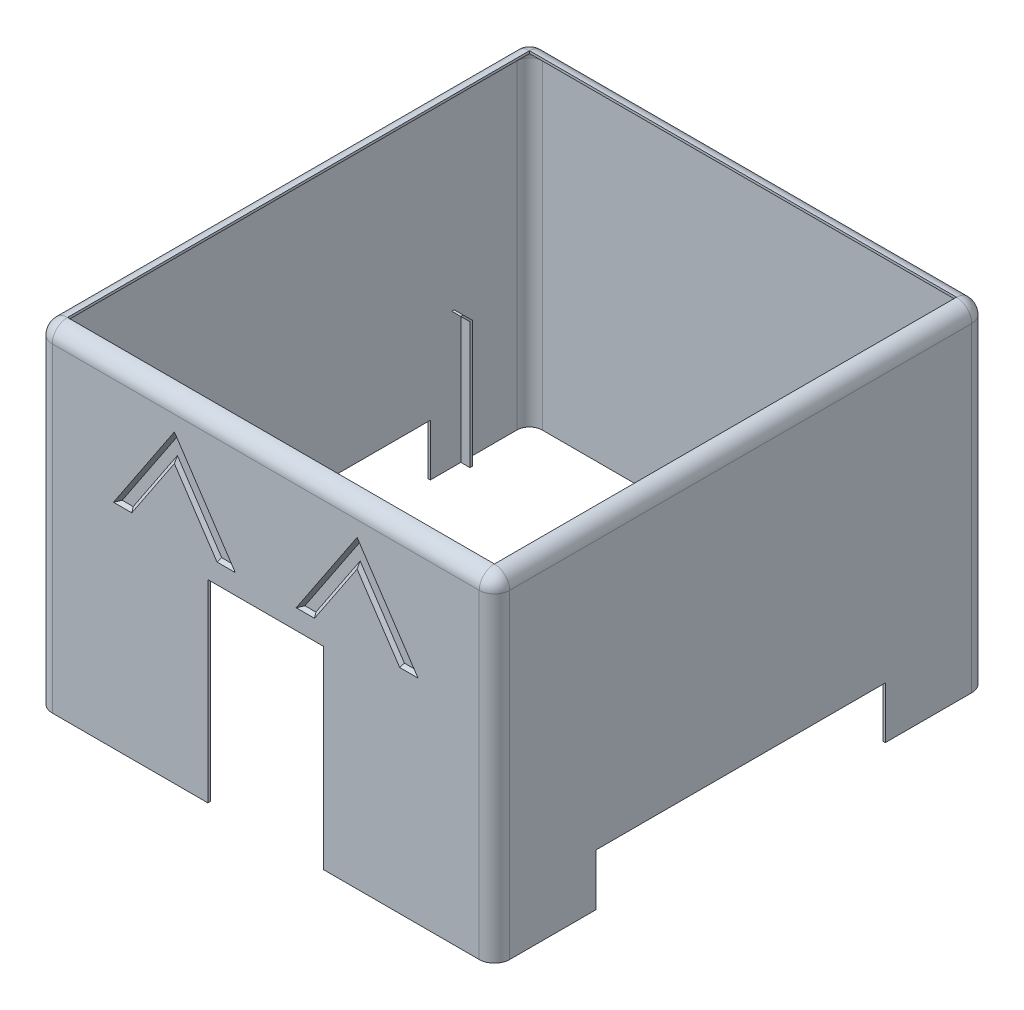
SolidWorks part; units mm, degrees
ref_plane "Front Plane" through (0, 0, 0) normal (0, 0, 1) x (1, 0, 0)
ref_plane "Top Plane" through (0, 0, 0) normal (0, 1, 0) x (1, 0, 0)
ref_plane "Right Plane" through (0, 0, 0) normal (1, 0, 0) x (0, 0, -1)
sketch "Sketch4" plane through (0, 0, 0) normal (0, 1, 0) x (1, 0, 0)
  line L1 (75.1, -80.8614) -> (-75.1, -80.8614)
  line L2 (75.1, -80.8614) -> (75.1, 80.8614)
  line L3 (75.1, 80.8614) -> (-75.1, 80.8614)
  line L4 (-75.1, -80.8614) -> (-75.1, 80.8614)
  line L5 (75.1, -80.8614) -> (-75.1, 80.8614) construction
  line L6 (75.1, 80.8614) -> (-75.1, -80.8614) construction
  line L7 (74.3, -80) -> (-74.3, -80) construction
  line L8 (74.3, -80) -> (74.3, 80) construction
  line L9 (74.3, 80) -> (-74.3, 80) construction
  line L10 (-74.3, -80) -> (-74.3, 80) construction
  line L11 (74.3, -80) -> (-74.3, 80) construction
  line L12 (74.3, 80) -> (-74.3, -80) construction
  point P0 (0, 0)
  point P6 (0, 0)
  dimension "D1" = 0.8
  dimension "D2" = 148.6
  dimension "D3" = 160
extrude "Boss-Extrude2" add sketch "Sketch4" along normal blind 110
sketch "Sketch5" plane through (0, 0, 80.8614) normal (0, 0, 1) x (1, 0, 0)
  line L0 (-50, 70) -> (-30, 100)
  line L1 (-30, 100) -> (-10, 70)
  line L2 (-10, 70) -> (-16.0093, 70)
  line L3 (-16.0093, 70) -> (-30, 90.9861)
  line L4 (-30, 90.9861) -> (-43.9907, 70)
  line L5 (-43.9907, 70) -> (-50, 70)
  line L8 (10, 70) -> (30, 100)
  line L9 (30, 100) -> (50, 70)
  line L10 (50, 70) -> (43.9907, 70)
  line L11 (43.9907, 70) -> (30, 90.9861)
  line L12 (30, 90.9861) -> (16.0093, 70)
  line L13 (16.0093, 70) -> (10, 70)
  line L14 (-10, 70) -> (10, 70) construction
  line L15 (0, 70) -> (0, 50) construction
  line L16 (-75.1, 110) -> (75.1, 110) construction
  point P13 (0, 0)
  point P15 (0, 17.7988)
  point P16 (35.5895, 20.909)
  point P17 (37.7841, 32.2479)
  point P20 (10, 70.8368)
  point P21 (0, 51.0851)
  point P22 (46.5626, 52.1824)
  point P24 (34.4922, 43.4039)
  point P33 (0, 40)
  point P34 (40.5274, 40)
  point P35 (25.7137, 40)
  point P36 (0, 0)
  point P37 (34.858, 44.3184)
  point P38 (25.7137, 40)
  point P39 (25, 40)
  point P40 (0, 23.8352)
  point P41 (0, 27.2622)
  dimension "D2" = 5
  dimension "D3" = 20
  dimension "D4" = 30
  dimension "D5" = 40
  dimension "D6" = 20
  dimension "D7" = 10
extrude "Cut-Extrude1" cut sketch "Sketch5" against normal blind 1
chamfer "Chamfer1" distance 1 angle 45 12 edges at (20, 85, 79.8614) (40, 85, 79.8614) (46.9954, 70, 79.8614) (36.9954, 80.4931, 79.8614) (23.0046, 80.4931, 79.8614) (13.0046, 70, 79.8614) (-40, 85, 79.8614) (-20, 85, 79.8614) (-13.0046, 70, 79.8614) (-23.0046, 80.4931, 79.8614) (-36.9954, 80.4931, 79.8614) (-46.9954, 70, 79.8614)
fillet "Fillet1" radius 5 8 edges at (-75.1, 55, -80.8614) (0, 110, -80.8614) (-75.1, 110, 0) (-75.1, 55, 80.8614) (75.1, 55, -80.8614) (75.1, 110, 0) (0, 110, 80.8614) (75.1, 55, 80.8614)
shell "Shell1" thickness 0.8 removed face at (0, 0, 0)
sketch "Sketch7" plane through (-74.3, 0, 0) normal (1, 0, 0) x (0, 0, -1)
  line L0 (-58.3, 0) -> (-58.3, 41.5)
  line L1 (75.8614, 0) -> (-75.8614, 0) construction
  line L2 (-58.3, 41.5) -> (-55.3, 44.5)
  line L3 (-55.3, 44.5) -> (-54.5, 44.5)
  line L4 (-54.5, 44.5) -> (-57.5, 41.5)
  line L5 (-57.5, 41.5) -> (-57.5, 0)
  line L6 (-57.5, 0) -> (-58.3, 0)
  line L7 (-57.5, 0) -> (57.5, 0)
  point P4 (0, 0)
  point P10 (0, 0)
  point P12 (-49.695, 13.1621)
  point P13 (-51.1741, 13.7163)
  point P14 (-58.3, 13.3268)
  line M10 (-75.8614, 0) -> (75.8614, 0)
  dimension "D1" = 0.8
  dimension "D2" = 135
  dimension "D3" = 3
  dimension "D4" = 115
  dimension "D5" = 41.5
extrude "Boss-Extrude3" add sketch "Sketch7" along normal blind 3 contours L5 L4 L3 L2 L0 M10 region at (-74.3, 22.25, 57.7989)
mirror "Mirror1" about plane through (0, 0, 0) normal (0, 0, 1) of "Boss-Extrude3"
mirror "Mirror2" about plane through (0, 0, 0) normal (1, 0, 0) of "Mirror1"
sketch "Sketch8" plane through (0, 0, 80.8614) normal (0, 0, 1) x (1, 0, 0)
  line L0 (-19, 0) -> (-19, 63.5)
  line L1 (-70.1, 0) -> (70.1, 0) construction
  line L4 (19, 63.5) -> (19, 0)
  line L5 (19, 0) -> (-19, 0)
  line L6 (-19, 63.5) -> (19, 63.5)
  point P4 (0, 63.5)
  point P5 (0, 0)
  dimension "D2" = 38
  dimension "D3" = 63.5
extrude "Cut-Extrude2" cut sketch "Sketch8" against normal up to surface (80.8614 mm away) up to plane "Front Plane"
sketch "Sketch9" plane through (-75.1, 0, 0) normal (-1, 0, 0) x (0, 0, 1)
  line L0 (-75.8614, 0) -> (75.8614, 0) construction
  line L1 (-47.5, 0) -> (47.5, 0)
  line L2 (-47.5, 0) -> (-47.5, 17)
  line L3 (-47.5, 17) -> (47.5, 17)
  line L4 (47.5, 0) -> (47.5, 17)
  line L5 (57.5, 41.5) -> (57.5, 0) construction
  line L6 (-57.5, 41.5) -> (-57.5, 0) construction
  point P6 (0, 0)
  dimension "D1" = 10
  dimension "D2" = 10
  dimension "D3" = 17
extrude "Cut-Extrude3" cut sketch "Sketch9" against normal through all
sketch "Sketch10" plane through (0, 110, 0) normal (0, 1, 0) x (1, 0, 0)
  line L4 (70.1, -75.8614) -> (70.1, 75.8614)
  line L5 (70.1, 75.8614) -> (-70.1, 75.8614)
  line L6 (-70.1, 75.8614) -> (-70.1, -75.8614)
  line L7 (-70.1, -75.8614) -> (70.1, -75.8614)
  line L8 (70.1, -75.8614) -> (70.1, 75.8614)
  line L9 (70.1, 75.8614) -> (-70.1, 75.8614)
  line L10 (-70.1, 75.8614) -> (-70.1, -75.8614)
  line L11 (-70.1, -75.8614) -> (70.1, -75.8614)
  dimension "D1" = 0
extrude "Cut-Extrude4" cut sketch "Sketch10" against normal blind 0.8
